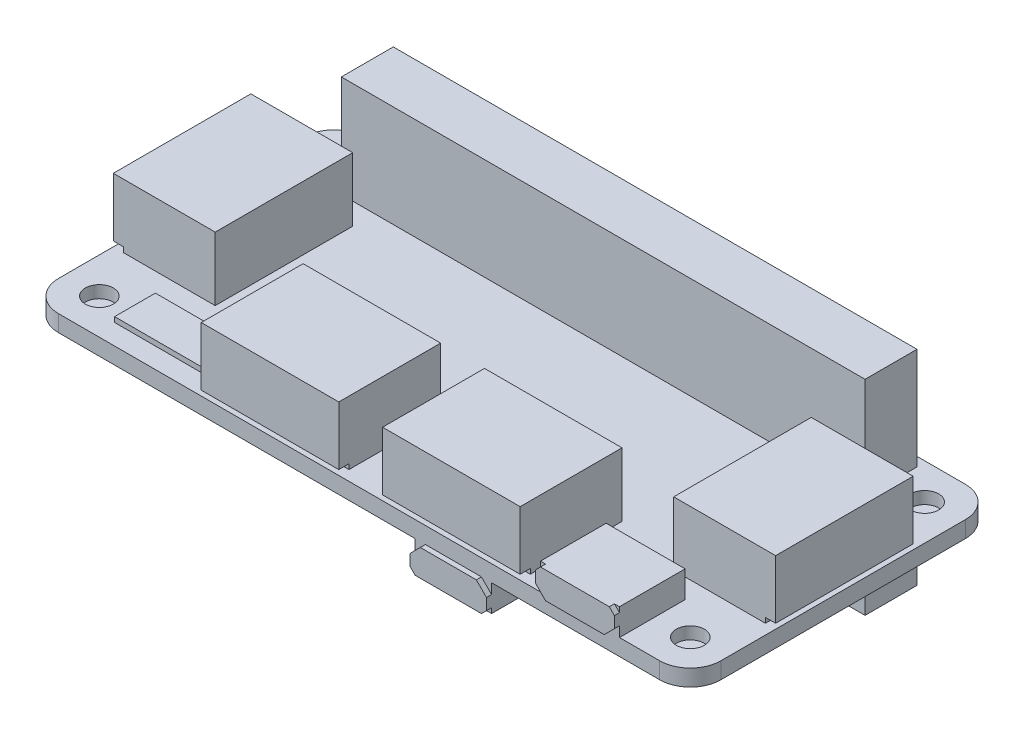
SolidWorks part; units mm, degrees
ref_plane "前视基准面" through (0, 0, 0) normal (0, 0, 1) x (1, 0, 0)
ref_plane "上视基准面" through (0, 0, 0) normal (0, 1, 0) x (1, 0, 0)
ref_plane "右视基准面" through (0, 0, 0) normal (1, 0, 0) x (0, 0, -1)
sketch "草图1" plane through (0, 0, 0) normal (0, 1, 0) x (1, 0, 0)
  line L1 (-29.5, 15) -> (29.5, 15)
  line L2 (-32.5, 12) -> (-32.5, -12)
  line L3 (-29.5, -15) -> (29.5, -15)
  line L4 (32.5, 12) -> (32.5, -12)
  line L5 (-32.5, 15) -> (32.5, -15) construction
  line L6 (-32.5, -15) -> (32.5, 15) construction
  arc A0 (29.5, 15) -> (32.5, 12) centre (29.5, 12) cw
  arc A1 (29.5, -15) -> (32.5, -12) centre (29.5, -12) ccw
  arc A2 (-32.5, -12) -> (-29.5, -15) centre (-29.5, -12) ccw
  arc A3 (-29.5, 15) -> (-32.5, 12) centre (-29.5, 12) ccw
  point P0 (0, 0)
  dimension "D3" = 3
  dimension "D1" = 65
  dimension "D2" = 30
extrude "凸台-拉伸1" add sketch "草图1" along normal blind 1.62
sketch "草图2" plane through (0, 1.62, 0) normal (0, 1, 0) x (1, 0, 0)
  line L0 (-29.5, -15) -> (29.5, -15) construction
  line L1 (32.5, -12) -> (32.5, 12) construction
  line L2 (29.5, 15) -> (-29.5, 15) construction
  circle A0 centre (29, -11.5) radius 1.375
  circle A1 centre (29, 11.5) radius 1.375
  circle A2 centre (-29, -11.5) radius 1.375
  circle A3 centre (-29, 11.5) radius 1.375
  dimension "D1" = 2.75
  dimension "D2" = 3.5
  dimension "D3" = 3.5
  dimension "D4" = 3.5
  dimension "D5" = 3.5
extrude "切除-拉伸1" cut sketch "草图2" against normal blind 1.2
sketch "草图11" plane through (0, 0, 0) normal (0, -1, 0) x (1, 0, 0)
  line L0 (29.5, -15) -> (-29.5, -15) construction
  line L1 (25.65, -14.1) -> (-25.75, -14.1)
  line L2 (25.65, -14.1) -> (25.65, -9)
  line L3 (25.65, -9) -> (-25.75, -9)
  line L4 (-25.75, -14.1) -> (-25.75, -9)
  line L5 (32.5, 12) -> (32.5, -12) construction
  dimension "D1" = 51.4
  dimension "D2" = 5.1
  dimension "D3" = 0.9
  dimension "D4" = 6.85
extrude "凸台-拉伸9" add sketch "草图11" along normal blind 8.45
sketch "草图12" plane through (0, 1.62, 0) normal (0, 1, 0) x (1, 0, 0)
  line L4 (25.65, 9) -> (25.65, 14.1)
  line L5 (-25.75, 9) -> (25.65, 9)
  line L6 (-25.75, 14.1) -> (-25.75, 9)
  line L7 (25.65, 14.1) -> (-25.75, 14.1)
  line L8 (25.65, 9) -> (25.65, 14.1)
  line L9 (-25.75, 9) -> (25.65, 9)
  line L10 (-25.75, 14.1) -> (-25.75, 9)
  line L11 (25.65, 14.1) -> (-25.75, 14.1)
  dimension "D1" = 0
extrude "凸台-拉伸10" add sketch "草图12" along normal blind 10
sketch "草图13" plane through (0, 1.62, 0) normal (0, 1, 0) x (1, 0, 0)
  line L0 (-32.5, 12) -> (-32.5, -12) construction
  line L1 (-32.5, 6.87) -> (-22.5, 6.87)
  line L2 (-32.5, 6.87) -> (-32.5, -6.63)
  line L3 (-32.5, -6.63) -> (-22.5, -6.63)
  line L4 (-22.5, 6.87) -> (-22.5, -6.63)
  line L5 (32.5, -12) -> (32.5, 12) construction
  line L6 (32.5, 6.87) -> (22.5, 6.87)
  line L7 (32.5, 6.87) -> (32.5, -6.63)
  line L8 (32.5, -6.63) -> (22.5, -6.63)
  line L9 (22.5, 6.87) -> (22.5, -6.63)
  line L10 (-29.5, -15) -> (29.5, -15) construction
  line L11 (-15.5, -15) -> (-2, -15)
  line L12 (-15.5, -15) -> (-15.5, -5)
  line L13 (-15.5, -5) -> (-2, -5)
  line L14 (-2, -15) -> (-2, -5)
  line L15 (29.5, 15) -> (-29.5, 15) construction
  line L16 (2.3, -15) -> (15.8, -15)
  line L17 (2.3, -15) -> (2.3, -5)
  line L18 (2.3, -5) -> (15.8, -5)
  line L19 (15.8, -15) -> (15.8, -5)
  point P28 (0, 0)
  dimension "D1" = 13.5
  dimension "D2" = 10
  dimension "D3" = 4.3
  dimension "D4" = 17
  dimension "D8" = 8.13
extrude "凸台-拉伸12" add sketch "草图13" along normal blind 6.25
sketch "草图14" plane through (0, 0, 15) normal (0, 0, 1) x (1, 0, 0)
  line L0 (-2, 7.87) -> (-2, 1.62) construction
  line L1 (-15.5, 1.62) -> (-2, 1.62)
  line L2 (-15.5, 1.62) -> (-15.5, 2.12)
  line L3 (-15.5, 2.12) -> (-2, 2.12)
  line L4 (-2, 1.62) -> (-2, 2.12)
  line L5 (15.8, 7.87) -> (15.8, 1.62) construction
  line L6 (2.3, 1.62) -> (15.8, 1.62)
  line L7 (2.3, 1.62) -> (2.3, 2.12)
  line L8 (2.3, 2.12) -> (15.8, 2.12)
  line L9 (15.8, 1.62) -> (15.8, 2.12)
  dimension "D1" = 0.5
  dimension "D2" = 0.5
extrude "切除-拉伸2" cut sketch "草图14" against normal blind 1
sketch "草图15" plane through (-32.5, 0, 0) normal (-1, 0, 0) x (0, 0, 1)
  line L0 (6.63, 7.87) -> (6.63, 1.62) construction
  line L1 (-6.87, 1.62) -> (6.63, 1.62)
  line L2 (-6.87, 1.62) -> (-6.87, 2.12)
  line L3 (-6.87, 2.12) -> (6.63, 2.12)
  line L4 (6.63, 1.62) -> (6.63, 2.12)
  dimension "D1" = 0.5
extrude "切除-拉伸3" cut sketch "草图15" against normal blind 1
sketch "草图16" plane through (32.5, 0, 0) normal (1, 0, 0) x (0, 0, -1)
  line L0 (6.87, 7.87) -> (6.87, 1.62) construction
  line L1 (-6.63, 1.62) -> (6.87, 1.62)
  line L2 (-6.63, 1.62) -> (-6.63, 2.12)
  line L3 (-6.63, 2.12) -> (6.87, 2.12)
  line L4 (6.87, 1.62) -> (6.87, 2.12)
  dimension "D1" = 0.5
extrude "切除-拉伸4" cut sketch "草图16" against normal blind 1
sketch "草图17" plane through (0, 1.62, 0) normal (0, 1, 0) x (1, 0, 0)
  line L0 (-29.5, -15) -> (29.5, -15) construction
  line L1 (17.8, -15) -> (25.55, -15)
  line L2 (17.8, -15) -> (17.8, -8.56)
  line L3 (17.8, -8.56) -> (25.55, -8.56)
  line L4 (25.55, -15) -> (25.55, -8.56)
  dimension "D1" = 6.44
  dimension "D2" = 7.75
  dimension "D3" = 2
extrude "凸台-拉伸13" add sketch "草图17" along normal blind 2.62
sketch "草图18" plane through (0, 0, 15) normal (0, 0, 1) x (1, 0, 0)
  line L0 (17.8, 2.62) -> (18.8, 1.62)
  line L1 (18.3, 4.24) -> (25.05, 4.24)
  line L2 (17.8, 3.74) -> (17.8, 2.62)
  line L3 (18.8, 1.62) -> (24.55, 1.62)
  line L4 (25.55, 3.74) -> (25.55, 2.62)
  line L5 (24.55, 1.62) -> (25.55, 2.62)
  line L6 (17.8, 3.74) -> (18.3, 4.24)
  line L7 (25.05, 4.24) -> (25.55, 3.74)
  point P0 (17.8, 4.24)
  point P1 (25.55, 1.62)
  point P2 (17.8, 1.62)
  point P3 (25.55, 4.24)
extrude "凸台-拉伸14" add sketch "草图18" along normal blind 0.5
sketch "草图19" plane through (0, 1.62, 0) normal (0, 1, 0) x (1, 0, 0)
  line L0 (-15.5, -5) -> (-15.5, -14) construction
  line L1 (-26, -9) -> (-17.5, -9)
  line L2 (-26, -9) -> (-26, -13)
  line L3 (-26, -13) -> (-17.5, -13)
  line L4 (-17.5, -9) -> (-17.5, -13)
  line L5 (-29.5, -15) -> (17.8, -15) construction
  dimension "D1" = 8.5
  dimension "D2" = 2
  dimension "D3" = 2
  dimension "D4" = 4
extrude "凸台-拉伸15" add sketch "草图19" along normal blind 0.5
sketch "草图20" plane through (0, 0, 0) normal (0, -1, 0) x (1, 0, 0)
  line L0 (-29.5, 15) -> (29.5, 15) construction
  line L1 (5.5, 15) -> (13, 15)
  line L2 (5.5, 15) -> (5.5, 9.8536)
  line L3 (5.5, 9.8536) -> (13, 9.8536)
  line L4 (13, 15) -> (13, 9.8536)
  line L5 (32.5, 12) -> (32.5, -12) construction
  dimension "D1" = 19.5
  dimension "D2" = 7.5
extrude "凸台-拉伸16" add sketch "草图20" along normal blind 2.62
sketch "草图21" plane through (0, 0, 15) normal (0, 0, 1) x (1, 0, 0)
  line L0 (13, -2.62) -> (13, 0) construction
  line L1 (6.5, 0) -> (12, 0)
  line L2 (5.5, -1) -> (5.5, -2.12)
  line L3 (6, -2.62) -> (12.5, -2.62)
  line L4 (13, -1) -> (13, -2.12)
  line L5 (12.5, -2.62) -> (13, -2.12)
  line L6 (5.5, -2.12) -> (6, -2.62)
  line L7 (5.5, -1) -> (6.5, 0)
  line L8 (12, 0) -> (13, -1)
  point P0 (5.5, 0)
  point P1 (13, -2.62)
  point P2 (5.5, -2.62)
  point P3 (13, 0)
extrude "凸台-拉伸17" add sketch "草图21" along normal blind 0.5
